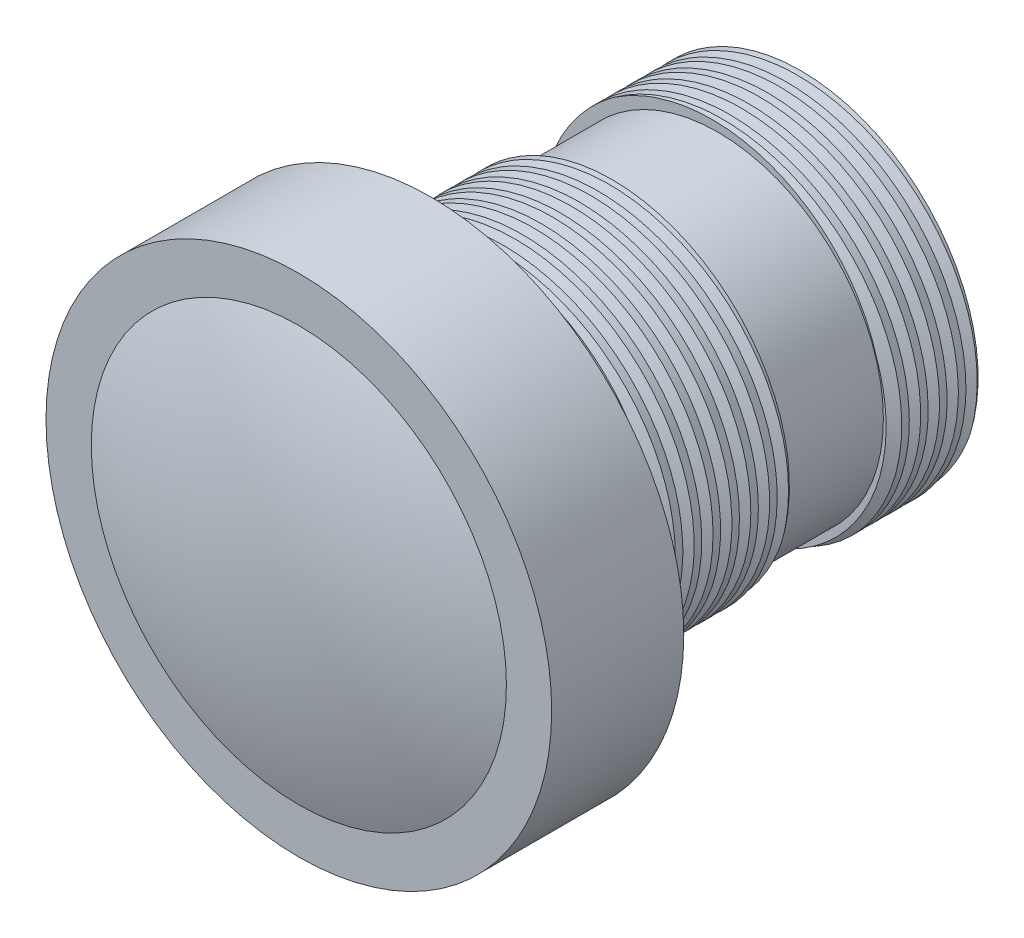
SolidWorks part; units mm, degrees
ref_plane "Front Plane" through (0, 0, 0) normal (0, 0, 1) x (1, 0, 0)
ref_plane "Top Plane" through (0, 0, 0) normal (0, 1, 0) x (1, 0, 0)
ref_plane "Right Plane" through (0, 0, 0) normal (1, 0, 0) x (0, 0, -1)
sketch "Sketch1" plane through (0, 0, 0) normal (0, 0, 1) x (1, 0, 0)
  circle A0 centre (0, 0) radius 5.969
  dimension "D1" = 11.938
extrude "Boss-Extrude1" add sketch "Sketch1" along normal blind 2.794
sketch "Sketch2" plane through (0, 0, 2.794) normal (0, 0, 1) x (1, 0, 0)
  circle A0 centre (0, 0) radius 5.5753
  dimension "D1" = 11.1506
extrude "Boss-Extrude2" add sketch "Sketch2" along normal offset from surface (9.652 mm away) 12.446 up to face at (5.969, 0, 0)
sketch "Sketch3" plane through (0, 0, 0) normal (0, 0, -1) x (-1, 0, 0)
  circle A0 centre (0, 0) radius 5.969
extrude "Boss-Extrude3" add sketch "Sketch3" against normal blind 4.064 from offset 6.35 offset against normal yes
sketch "Sketch4" plane through (0, 0, 12.446) normal (0, 0, 1) x (1, 0, 0)
  circle A0 centre (0, 0) radius 5.6007
  circle A1 centre (0, 0) radius 5.5753 construction
  dimension "D1" = 0.0254
curve "Helix/Spiral1" pitch 0.635 height 13.1762 radius 5.6007 centre (0, 0, 12.446) axis (0, 0, -1) start towards (0, 1, 0)
sketch "Sketch5" plane through (0, 0, 0) normal (1, 0, 0) x (0, 0, -1)
  line L0 (-12.446, 5.6007) -> (-12.6365, 5.969)
  line L1 (-12.6365, 5.969) -> (-12.2555, 5.969) construction
  line L2 (-12.2555, 5.969) -> (-12.446, 5.6007)
  line L3 (-6.35, 5.969) -> (-10.414, 5.969) construction
  line L4 (-12.6365, 5.969) -> (-12.6365, 6.923)
  line L5 (-12.6365, 6.923) -> (-12.2555, 6.923)
  line L6 (-12.2555, 6.923) -> (-12.2555, 5.969)
  point P2 (-12.446, 5.969)
  dimension "D1" = 0.381
sweep "Cut-Sweep2" cut profiles "Sketch5" path "Helix/Spiral1" align with end faces yes
sketch "Sketch6" plane through (0, 0, 0) normal (0, 0, -1) x (-1, 0, 0)
  circle A0 centre (0, 0) radius 2.667
  dimension "D1" = 5.334
extrude "Cut-Extrude1" cut sketch "Sketch6" against normal through all
sketch "Sketch7" plane through (0, 0, 12.446) normal (0, 0, 1) x (1, 0, 0)
  circle A0 centre (0, 0) radius 8.509
  circle A1 centre (0, 0) radius 2.667
  dimension "D1" = 17.018
extrude "Boss-Extrude4" add sketch "Sketch7" along normal blind 4.445
sketch "Sketch8" plane through (0, 0, 16.891) normal (0, 0, 1) x (1, 0, 0)
  circle A0 centre (0, 0) radius 6.985
  dimension "D1" = 13.97
extrude "Cut-Extrude2" cut sketch "Sketch8" against normal blind 0.508
sketch "Sketch9" plane through (0, 0, 0) normal (1, 0, 0) x (0, 0, -1)
  line L0 (-16.891, 6.985) -> (-13.5014, 6.985)
  line L1 (-16.891, 8.509) -> (-16.891, -8.509) construction
  line L2 (-13.5014, 6.985) -> (-13.5014, 0)
  line L3 (-13.5014, 0) -> (-18.161, 0)
  arc A0 (-16.891, 6.985) -> (-18.161, 0) centre (1.6827, 0) ccw
  point P2 (-18.161, 0)
  dimension "D1" = 18.161
revolve "Revolve1" add sketch "Sketch9" angle 360 about L3
